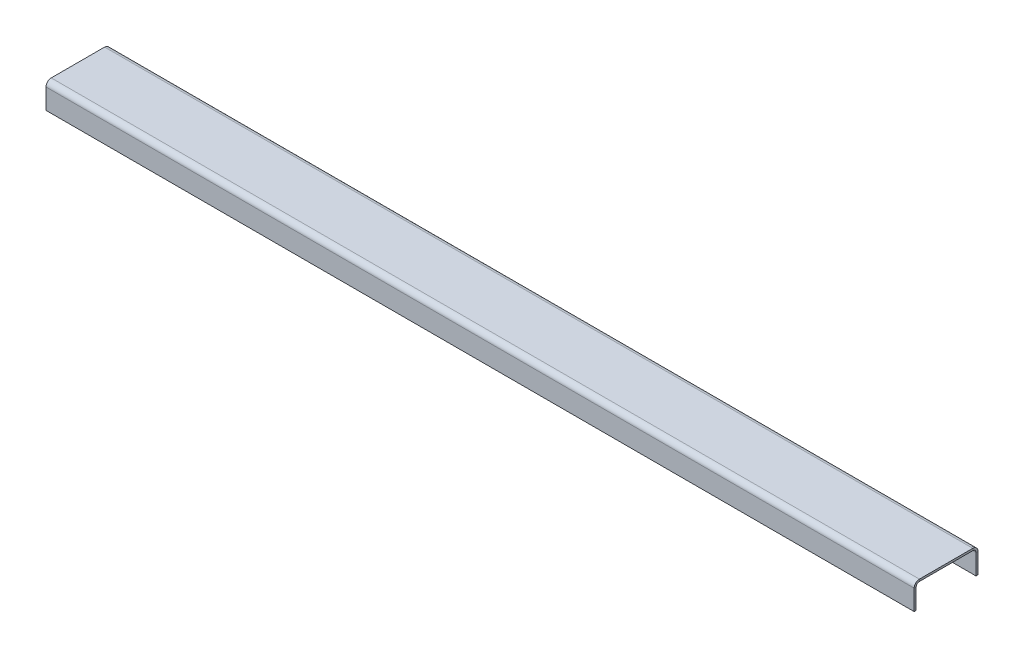
SolidWorks part; units mm, degrees
note: The reader was unsure of these and kept them because the rebuilt part matched: thickness of "Base-Flange1", "Edge-Flange1", "Sheet-Metal1", "Sheet-Metal4"; flange length of "Edge-Flange1".
material "5052-H32"
ref_plane "Front Plane" through (0, 0, 0) normal (0, 0, 1) x (1, 0, 0)
ref_plane "Top Plane" through (0, 0, 0) normal (0, 1, 0) x (1, 0, 0)
ref_plane "Right Plane" through (0, 0, 0) normal (1, 0, 0) x (0, 0, -1)
sketch "Sketch1" plane through (0, 0, 0) normal (0, 1, 0) x (1, 0, 0)
  line L1 (0, 0) -> (863.6, 0)
  line L2 (0, 0) -> (0, 63.5)
  line L3 (0, 63.5) -> (863.6, 63.5)
  line L4 (863.6, 0) -> (863.6, 63.5)
  dimension "D1" = 63.5
  dimension "D2" = 863.6
base flange "Base-Flange1" sketch "Sketch1" thickness 2.032 reverse thickness direction no parameters "D1"=3.175
edge flange "Edge-Flange1" sketch "Sketch6" flange profiles "Sketch6", "Sketch7" flange angle 90 flange length 25.4 flange position material inside bend radius 3.175 thickness 2.032 relief rectangular parameters "D6"=10, "D8"=1
sketch "Sketch6" plane through (0, -2.032, 0) normal (0, 0, 1) x (-1, 0, 0)
  line L0 (0, 0) -> (-863.6, 0) construction
  line L1 (0, 0) -> (-863.6, 0)
  line L2 (-863.6, 0) -> (-863.6, 23.368)
  line L3 (-863.6, 23.368) -> (0, 23.368)
  line L4 (0, 23.368) -> (0, 0)
sketch "Sketch7" plane through (0, -2.032, -63.5) normal (0, 0, -1) x (1, 0, 0)
  line L0 (863.6, 0) -> (0, 0) construction
  line L1 (863.6, 0) -> (0, 0)
  line L2 (0, 0) -> (0, 23.368)
  line L3 (0, 23.368) -> (863.6, 23.368)
  line L4 (863.6, 23.368) -> (863.6, 0)
bend "EdgeBend1" bend radius 3.175 bend angle 90 parameters "D5"=1
bend "EdgeBend2" bend radius 3.175 bend angle 90 parameters "D5"=2
sketch "Sketch8" plane through (0, 0, -63.5) normal (0, 0, -1) x (-1, 0, 0)
  line L0 (-863.6, -5.207) -> (-863.6, -25.4) construction
  line L1 (-863.6, -25.4) -> (0, -25.4) construction
  line L2 (0, -25.4) -> (0, -5.207) construction
  line L3 (-431.8, -25.4) -> (-431.8, 0) construction
  line L4 (-863.6, 0) -> (0, 0) construction
  circle A0 centre (-806.45, -15.875) radius 2.4575
  circle A1 centre (-556.6833, -15.875) radius 2.4575
  circle A2 centre (-306.9167, -15.875) radius 2.4575
  circle A3 centre (-57.15, -15.875) radius 2.4575
  circle A4 centre (-687.3392, -15.875) radius 3.3734
  circle A5 centre (-615.9652, -15.875) radius 3.3734
  circle A6 centre (-247.6348, -15.875) radius 3.3734
  circle A7 centre (-176.2608, -15.875) radius 3.3734
  dimension "D2" = 9.525
  dimension "D3" = 4.9149
  dimension "D7" = 6.7469
  dimension "D10" = 6.7469
  dimension "D1" = 57.15
  dimension "D5" = 57.15
  dimension "D6" = 176.2608
  dimension "D8" = 9.525
  dimension "D9" = 71.374
  dimension "D11" = 9.525
  dimension "D12" = 431.8
  dimension "D4" = 4
ref_plane "Plane1" through (0, 0, -31.75) normal (0, 0, -1) x (-1, 0, 0)
sketch "Bend-Lines1" [suppressed] plane through (0, 0, 0) normal (0, 1, 0) x (1, 0, 0)
sketch "Bounding-Box1" [suppressed] plane through (0, 0, 0) normal (0, 1, 0) x (1, 0, 0)
sheet metal parameters "Sheet-Metal1" thickness 2.032 parameters "D1"=3.175
flat pattern "Flat-Pattern1" [suppressed]
sketch "Bend-Lines2" plane through (0, 0, 0) normal (0, 1, 0) x (1, 0, 0)
sketch3d "Bounding-Box2" [suppressed]
  line L0 (863.6, 63.5, 0) -> (0, 63.5, 0) construction
  line L1 (863.6, 0, 0) -> (0, 0, 0) construction
  line L2 (863.6, 63.5, 0) -> (863.6, 0, 0) construction
  line L3 (0, 63.5, 0) -> (0, 0, 0) construction
sheet metal parameters "Sheet-Metal4" thickness 2.032 parameters "D1"=3.175, "D7"=3.175
flat pattern "Flat-Pattern1"
sketch "Bend-Lines2" plane through (0, 0, 0) normal (0, 1, 0) x (1, 0, 0)
  line L0 (863.6, 61.5846) -> (0, 61.5846) construction
  line L1 (0, 1.9154) -> (863.6, 1.9154) construction
  line L2 (863.6, 61.5846) -> (0, 61.5846) construction
  line L3 (0, 1.9154) -> (863.6, 1.9154) construction
sketch3d "Bounding-Box2" [suppressed]
  line L0 (863.6, 85.0692, 0) -> (0, 85.0692, 0) construction
  line L1 (863.6, -21.5692, 0) -> (0, -21.5692, 0) construction
  line L2 (863.6, 85.0692, 0) -> (863.6, -21.5692, 0) construction
  line L3 (0, 85.0692, 0) -> (0, -21.5692, 0) construction
bend of the flat pattern "Flatten-<EdgeBend1>1"
bend of the flat pattern "Flatten-<EdgeBend2>1"
